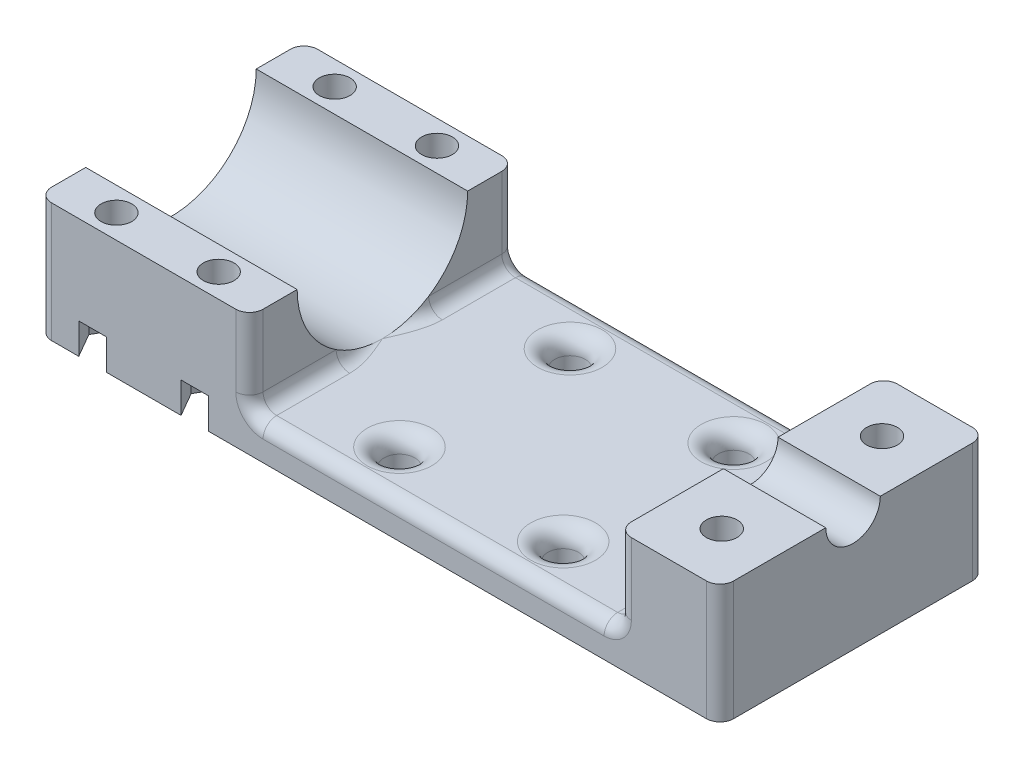
SolidWorks part; units mm, degrees
ref_plane "Front Plane" through (0, 0, 0) normal (0, 0, 1) x (1, 0, 0)
ref_plane "Top Plane" through (0, 0, 0) normal (0, 1, 0) x (1, 0, 0)
ref_plane "Right Plane" through (0, 0, 0) normal (1, 0, 0) x (0, 0, -1)
sketch "Sketch1" plane through (0, 0, 0) normal (0, 1, 0) x (1, 0, 0)
  line L1 (0, 0) -> (100, 0)
  line L2 (0, 0) -> (0, -39)
  line L3 (0, -39) -> (100, -39)
  line L4 (100, 0) -> (100, -39)
  dimension "D1" = 100
  dimension "D2" = 39
extrude "Boss-Extrude1" add sketch "Sketch1" along normal blind 5
sketch "Sketch2" plane through (0, 5, 0) normal (0, 1, 0) x (1, 0, 0)
  line L1 (0, 0) -> (31, 0)
  line L2 (0, 0) -> (0, -7)
  line L3 (0, -7) -> (31, -7)
  line L4 (31, 0) -> (31, -7)
  line L5 (0, -39) -> (31, -39)
  line L6 (0, -39) -> (0, -32)
  line L7 (0, -32) -> (31, -32)
  line L8 (31, -39) -> (31, -32)
  dimension "D1" = 7
  dimension "D2" = 31
extrude "Boss-Extrude2" add sketch "Sketch2" along normal blind 12.5
sketch "Sketch7" plane through (0, 17.5, 0) normal (0, 1, 0) x (1, 0, 0)
  line L0 (0, -32) -> (0, -39) construction
  line L1 (0, -19.5) -> (31, -19.5) construction
  line L2 (31, -39) -> (31, -32) construction
  line L3 (0, -7) -> (0, -32) construction
  line L4 (0, -39) -> (31, -39) construction
  circle A0 centre (8, -35.5) radius 2.25
  circle A1 centre (23, -35.5) radius 2.25
  circle A2 centre (8, -3.5) radius 2.25
  circle A5 centre (23, -3.5) radius 2.25
  point P13 (31, -35.5)
  dimension "D1" = 4.5
  dimension "D2" = 8
  dimension "D3" = 8
extrude "Cut-Extrude2" cut sketch "Sketch7" against normal up to surface (17.5 mm away) up to face at (50, 0, 19.5)
sketch "Sketch9" plane through (0, 0, 0) normal (0, -1, 0) x (1, 0, 0)
  line L0 (100, 0) -> (0, 0) construction
  line L1 (10.0207, 7) -> (5.9793, 7)
  line L2 (5.9793, 7) -> (3.9585, 3.5)
  line L3 (3.9585, 3.5) -> (5.9793, 0)
  line L4 (5.9793, 0) -> (10.0207, 0)
  line L5 (10.0207, 0) -> (12.0415, 3.5)
  line L6 (12.0415, 3.5) -> (10.0207, 7)
  line L7 (0, 19.5) -> (100, 19.5) construction
  line L8 (20.9793, 7) -> (18.9585, 3.5)
  line L9 (18.9585, 3.5) -> (20.9793, 0)
  line L10 (20.9793, 0) -> (25.0207, 0)
  line L11 (25.0207, 0) -> (27.0415, 3.5)
  line L12 (27.0415, 3.5) -> (25.0207, 7)
  line L13 (25.0207, 7) -> (20.9793, 7)
  line L14 (0, 0) -> (0, 39) construction
  line L15 (100, 39) -> (100, 0) construction
  line L16 (25.0207, 32) -> (20.9793, 32)
  line L17 (27.0415, 35.5) -> (25.0207, 32)
  line L18 (25.0207, 39) -> (27.0415, 35.5)
  line L19 (20.9793, 39) -> (25.0207, 39)
  line L20 (18.9585, 35.5) -> (20.9793, 39)
  line L21 (20.9793, 32) -> (18.9585, 35.5)
  line L22 (12.0415, 35.5) -> (10.0207, 32)
  line L23 (10.0207, 39) -> (12.0415, 35.5)
  line L24 (5.9793, 39) -> (10.0207, 39)
  line L25 (3.9585, 35.5) -> (5.9793, 39)
  line L26 (5.9793, 32) -> (3.9585, 35.5)
  line L27 (10.0207, 32) -> (5.9793, 32)
  circle A0 centre (8, 3.5) radius 3.5 construction
  circle A2 centre (23, 3.5) radius 3.5 construction
  circle A3 centre (23, 35.5) radius 3.5 construction
  circle A4 centre (8, 35.5) radius 3.5 construction
  circle A5 centre (8, 3.5) radius 2.25 construction
  circle A6 centre (23, 3.5) radius 2.25 construction
  dimension "D1" = 7
sketch "Sketch15" plane through (100, 0, 0) normal (1, 0, 0) x (0, 0, -1)
  line L0 (-39, 5) -> (-39, 17.5)
  line L1 (-39, 17.5) -> (-23.5, 17.5)
  line L4 (-15.5, 17.5) -> (0, 17.5)
  line L5 (0, 17.5) -> (0, 5)
  line L6 (0, 5) -> (-39, 5)
  arc A0 (-23.5, 17.5) -> (-15.5, 17.5) centre (-19.5, 17.5) ccw
  dimension "D1" = 4
  dimension "D4" = 12.5
extrude "Boss-Extrude8" add sketch "Sketch15" against normal blind 15
extrude "Cut-Extrude3" cut sketch "Sketch9" against normal blind 4.5
sketch "Sketch17" plane through (0, 17.5, 0) normal (0, 1, 0) x (1, 0, 0)
  line L0 (100, -23.5) -> (100, -39) construction
  line L1 (85, -39) -> (100, -39) construction
  line L2 (100, -19.5) -> (85, -19.5) construction
  line L3 (100, -23.5) -> (100, -15.5) construction
  line L4 (85, -15.5) -> (85, -23.5) construction
  circle A0 centre (92.5, -31.25) radius 2.25
  circle A1 centre (23, -35.5) radius 2.25 construction
  circle A2 centre (92.5, -7.75) radius 2.25
  point P8 (100, -31.25)
  point P12 (92.5, -39)
extrude "Cut-Extrude4" cut sketch "Sketch17" against normal up to surface (17.5 mm away) up to face at (20.4286, 0, 19.5)
sketch "Sketch18" plane through (0, 0, 0) normal (0, -1, 0) x (1, 0, 0)
  line L0 (100, 0) -> (25.0207, 0) construction
  line L1 (96.5415, 7.75) -> (94.5207, 11.25)
  line L2 (94.5207, 11.25) -> (90.4793, 11.25)
  line L3 (90.4793, 11.25) -> (88.4585, 7.75)
  line L4 (88.4585, 7.75) -> (90.4793, 4.25)
  line L5 (90.4793, 4.25) -> (94.5207, 4.25)
  line L6 (94.5207, 4.25) -> (96.5415, 7.75)
  line L9 (25.0207, 0) -> (27.0415, 3.5) construction
  line L10 (100, 19.5) -> (87.4118, 19.5) construction
  line L11 (100, 39) -> (100, 0) construction
  line L12 (94.5207, 34.75) -> (96.5415, 31.25)
  line L13 (90.4793, 34.75) -> (94.5207, 34.75)
  line L14 (88.4585, 31.25) -> (90.4793, 34.75)
  line L15 (90.4793, 27.75) -> (88.4585, 31.25)
  line L16 (94.5207, 27.75) -> (90.4793, 27.75)
  line L17 (96.5415, 31.25) -> (94.5207, 27.75)
  circle A0 centre (92.5, 7.75) radius 3.5 construction
  circle A1 centre (92.5, 7.75) radius 2.25 construction
  circle A2 centre (92.5, 31.25) radius 3.5 construction
extrude "Cut-Extrude5" cut sketch "Sketch18" against normal blind 4.5
sketch "Sketch19" plane through (0, 5, 0) normal (0, 1, 0) x (1, 0, 0)
  line L1 (0, -7) -> (0, -32) construction
  line L2 (0, -19.5) -> (85, -19.5) construction
  line L4 (85, -15.5) -> (85, -23.5) construction
  circle A0 centre (46, -32) radius 2.25
  circle A1 centre (70, -32) radius 2.25
  circle A2 centre (70, -7) radius 2.25
  circle A3 centre (46, -7) radius 2.25
  dimension "D1" = 4.5
  dimension "D2" = 15
  dimension "D3" = 15
extrude "Cut-Extrude6" cut sketch "Sketch19" against normal up to surface (5 mm away) up to face at (92.5, 0, 7.75)
sketch "Sketch20" plane through (0, 0, 0) normal (-1, 0, 0) x (0, 0, 1)
  line L0 (7, 4.8) -> (7, 17.5)
  line L2 (7, 4.8) -> (32, 4.8)
  line L3 (32, 4.8) -> (32, 17.5)
  line L7 (9.25, 5) -> (4.75, 5) construction
  line L8 (0, 0) -> (39, 0) construction
  line L9 (32, 17.5) -> (32, 5) construction
  arc A0 (7, 17.5) -> (32, 17.5) centre (19.5, 17.5) ccw
  dimension "D1" = 12.5
  dimension "D2" = 4.8
extrude "Boss-Extrude9" add sketch "Sketch20" against normal up to surface (31 mm away) up to face at (31, 11.25, 35.5)
fillet "Fillet1" radius 2.5 4 edges at (46, 5, 34.25) (46, 5, 4.75) (70, 5, 4.75) (70, 5, 34.25)
fillet "Fillet2" radius 2 3 edges at (31, 5, 29.25) (31, 5, 9.75) (85, 5, 19.5)
fillet "Fillet3" radius 2 14 edges at (84.4142, 5.5858, 39) (31.5858, 5.5858, 39) (84.4142, 5.5858, 0) (31.5858, 5.5858, 0) (100, 8.75, 0) (100, 8.75, 39) (85, 12.25, 0) (85, 12.25, 39) (58, 5, 39) (31, 12.25, 39) (0, 8.75, 39) (0, 8.75, 0) (58, 5, 0) (31, 12.25, 0)
